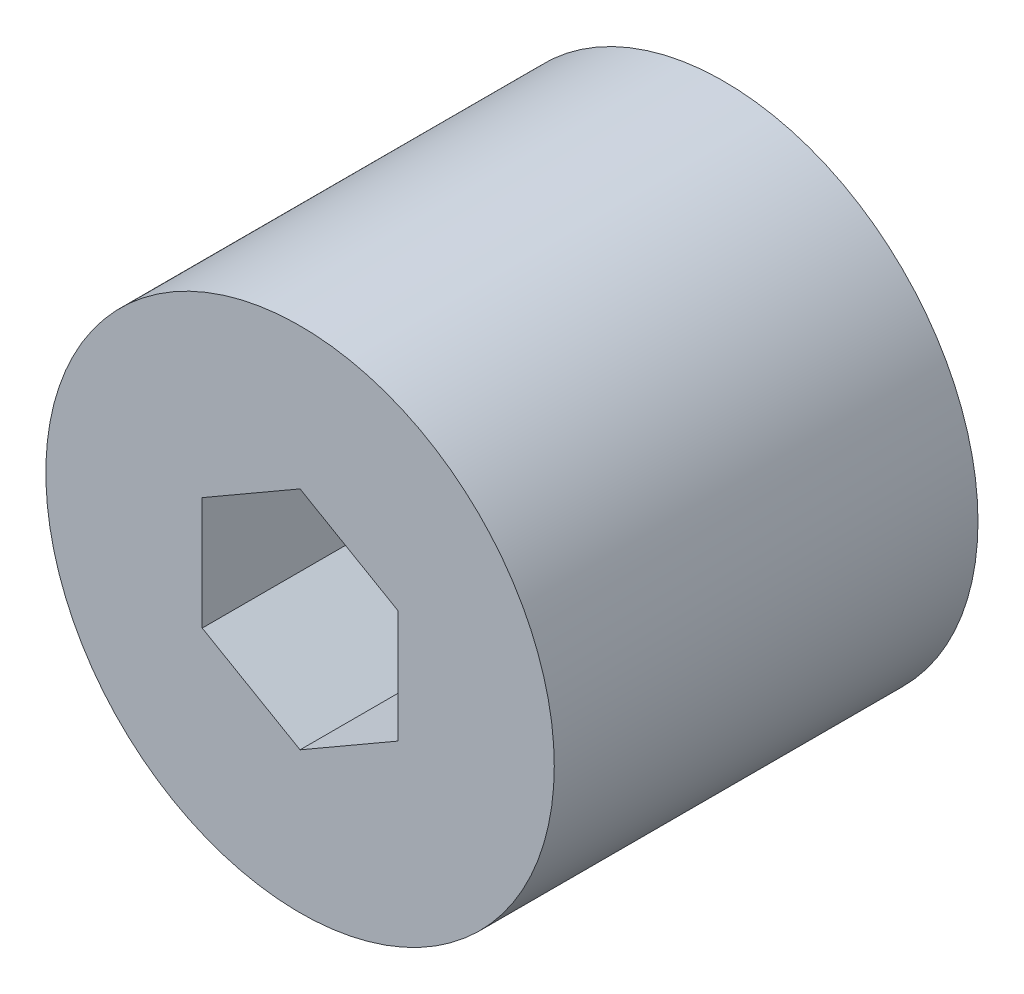
SolidWorks part; units mm, degrees
ref_plane "Piano frontale" through (0, 0, 0) normal (0, 0, 1) x (1, 0, 0)
ref_plane "Piano superiore" through (0, 0, 0) normal (0, 1, 0) x (1, 0, 0)
ref_plane "Piano destro" through (0, 0, 0) normal (1, 0, 0) x (0, 0, -1)
sketch "Schizzo1" plane through (0, 0, 0) normal (0, 0, 1) x (1, 0, 0)
  circle A0 centre (-6.4049, 0) radius 4.5
  point P2 (0, 0)
  dimension "D1" = 9
extrude "Estrusione-Estrusione1" add sketch "Schizzo1" along normal blind 7.5
sketch "Schizzo3" plane through (0, 0, 7.5) normal (0, 0, 1) x (1, 0, 0)
  line L0 (-6.4049, 4.5) -> (-6.4049, -4.5) construction
  line L7 (-6.4049, 2) -> (-8.1369, 1)
  line L8 (-8.1369, 1) -> (-8.1369, -1)
  line L9 (-8.1369, -1) -> (-6.4049, -2)
  line L10 (-6.4049, -2) -> (-4.6728, -1)
  line L11 (-4.6728, -1) -> (-4.6728, 1)
  line L12 (-4.6728, 1) -> (-6.4049, 2)
  circle A0 centre (-6.4049, 0) radius 1.7321 construction
  circle A1 centre (-6.4049, 0) radius 4.5 construction
  point P14 (-6.4049, -4.5)
  dimension "D1" = 2
  dimension "D2" = 9
extrude "Taglio-Estrusione1" cut sketch "Schizzo3" against normal blind 7.5
sketch "Schizzo4" plane through (0, 0, 7.5) normal (0, 0, 1) x (1, 0, 0)
  circle A0 centre (-6.4049, 0) radius 4.5
